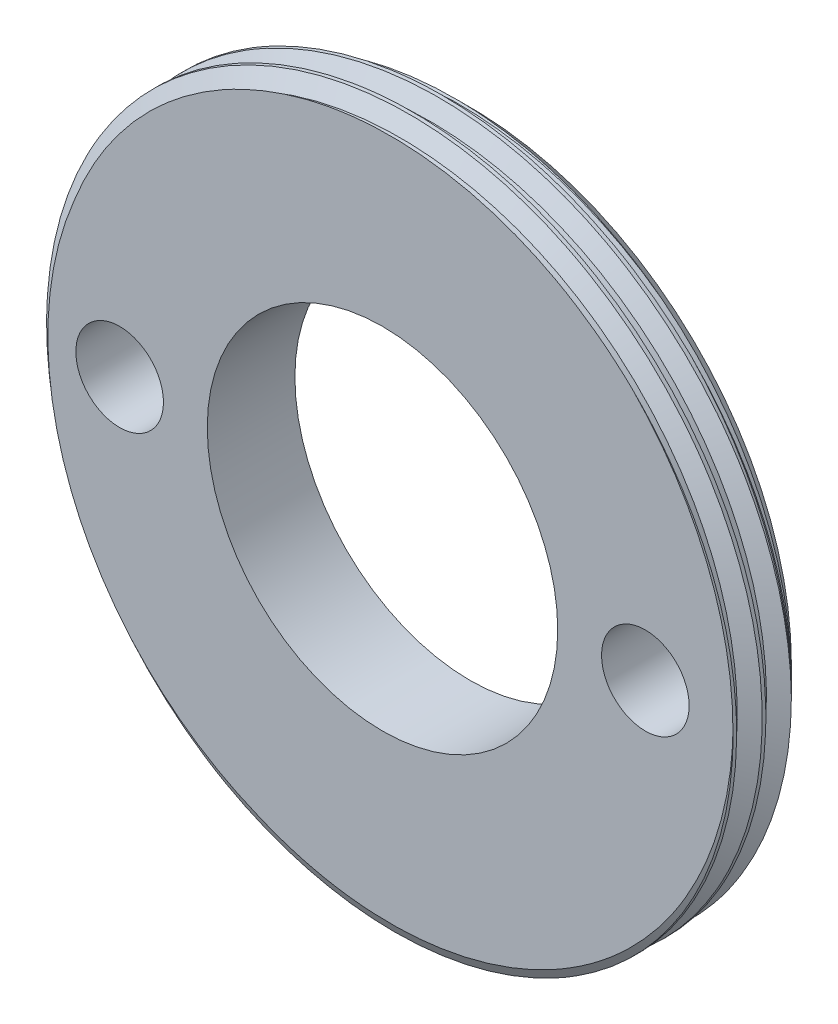
SolidWorks part; units mm, degrees
ref_plane "Спереди" through (0, 0, 0) normal (0, 0, 1) x (1, 0, 0)
ref_plane "Сверху" through (0, 0, 0) normal (0, 1, 0) x (1, 0, 0)
ref_plane "Справа" through (0, 0, 0) normal (1, 0, 0) x (0, 0, -1)
sketch "Эскиз1" plane through (0, 0, 0) normal (0, 0, 1) x (1, 0, 0)
  circle A0 centre (0, 0) radius 6
  dimension "D1" = 12
extrude "Бобышка-Вытянуть1" add sketch "Эскиз1" along normal blind 1.5
chamfer "Фаска3" distance 0.5 angle 45 1 edges at (6, 0, 0)
sketch "Эскиз2" plane through (0, 0, 1.5) normal (0, 0, 1) x (1, 0, 0)
  circle A0 centre (0, 0) radius 3
  dimension "D1" = 6
extrude "Вырез-Вытянуть1" cut sketch "Эскиз2" against normal through all
sketch "Эскиз4" plane through (0, 0, 1.5) normal (0, 0, 1) x (1, 0, 0)
  line L5 (-3, 0) -> (-6, 0) construction
  line L6 (0, 6) -> (0, -6) construction
  circle A0 centre (-4.5, 0) radius 0.75
  circle A2 centre (0, 0) radius 3 construction
  circle A3 centre (0, 0) radius 6 construction
  circle A4 centre (4.5, 0) radius 0.75
  point P4 (-3, 0)
  dimension "D1" = 1.5
extrude "Вырез-Вытянуть3" cut sketch "Эскиз4" against normal through all and the other way blind 0.5
thread "Резьба1" pitch 0.5 method cut profile "Профиль резьбы1" start angle 0, offset 2, length 10, pitch 0.5, diameter 12
ref_plane "Плоскость1" through (6, 0, -1.5) normal (0, -1, 0) x (1, 0, 0)
sketch "Профиль резьбы1" plane through (6, 0, -1.5) normal (0, -1, 0) x (1, 0, 0)
  line L0 (0, 0) -> (0, 0.5) construction
  line L11 (0, 0) -> (0, 0.4375)
  line L12 (0, 0.4375) -> (-0.2706, 0.2812)
  line L13 (-0.2706, 0.2812) -> (-0.2706, 0.1562)
  line L15 (-0.2706, 0.1562) -> (0, 0)
  line L17 (-0.2706, 0.2187) -> (0, 0.2187) construction
  point P2 (0, 0)
  dimension "Pitch" = 0.5
  dimension "Profile_Angle" = 60
  dimension "Profile_Land" = 0.125
  dimension "Profile_Height" = 0.2706
